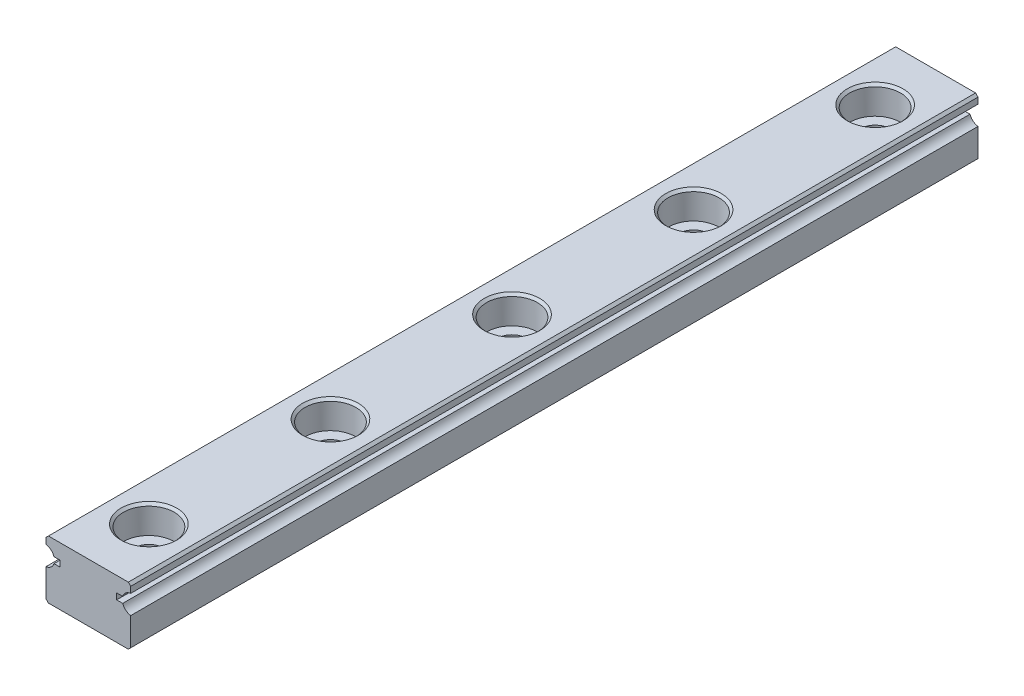
SolidWorks part; units mm, degrees
ref_plane "Спереди" through (0, 0, 0) normal (0, 0, 1) x (1, 0, 0)
ref_plane "Сверху" through (0, 0, 0) normal (0, 1, 0) x (1, 0, 0)
ref_plane "Справа" through (0, 0, 0) normal (1, 0, 0) x (0, 0, -1)
sketch "Sketch1" plane through (0, 0, 0) normal (0, 0, 1) x (1, 0, 0)
  line L0 (0, 0) -> (0, 4.3706) construction
  line L1 (-3.3, -2.4) -> (3.3, -2.4)
  line L2 (-3.5, -2.2) -> (-3.5, 0.1063)
  line L3 (-3.3, 2.4) -> (3.3, 2.4)
  line L4 (3.5, -2.2) -> (3.5, 0.1063)
  line L5 (-3.5, -2.4) -> (3.5, 2.4) construction
  line L6 (-3.5, 2.4) -> (3.5, -2.4) construction
  line L7 (-3.5, 1.6937) -> (-3.5, 2.2)
  line L8 (3.5, 1.6937) -> (3.5, 2.2)
  line L9 (-3.5, -2.2) -> (-3.3, -2.4)
  line L10 (3.3, -2.4) -> (3.5, -2.2)
  line L11 (3.3, 2.4) -> (3.5, 2.2)
  line L12 (-3.5, 2.2) -> (-3.3, 2.4)
  line L13 (2.8401, 0.65) -> (2.3401, 0.65)
  line L14 (-2.8401, 0.65) -> (-2.3401, 0.65)
  line L15 (2.3401, 0.65) -> (2.3401, 1.15)
  line L16 (-2.8401, 1.15) -> (-2.3401, 1.15)
  line L17 (-2.3401, 0.65) -> (-2.3401, 1.15)
  line L18 (2.8401, 1.15) -> (2.3401, 1.15)
  arc A0 (-3.5, 1.6937) -> (-2.8401, 1.15) centre (-3.6, 0.9) cw
  arc A1 (3.5, 1.6937) -> (2.8401, 1.15) centre (3.6, 0.9) ccw
  arc A2 (-2.8401, 0.65) -> (-3.5, 0.1063) centre (-3.6, 0.9) cw
  arc A3 (2.8401, 0.65) -> (3.5, 0.1063) centre (3.6, 0.9) ccw
  point P0 (0, 0)
  dimension "D4" = 0.8
  dimension "D5" = 0.1
  dimension "D1" = 7
  dimension "D2" = 4.8
  dimension "D3" = 1.5
  dimension "D6" = 0.5
  dimension "D7" = 0.5
extrude "Extrude1" add sketch "Sketch1" along normal blind 70
sketch "Sketch2" plane through (0, 2.4, 0) normal (0, 1, 0) x (1, 0, 0)
  line L0 (0, 0) -> (0, -5) construction
  circle A0 centre (0, -5) radius 1.2
  circle A1 centre (0, -5) radius 2.1
  dimension "D1" = 2.4
  dimension "D2" = 4.2
  dimension "D3" = 5
extrude "Extrude2" cut sketch "Sketch2" against normal up to next contours A0 region at (0, 2.4, 5)
extrude "Extrude4" cut sketch "Sketch" against normal blind 2.3
sketch "Sketch" plane through (0, 2.4, 0) normal (0, 1, 0) x (1, 0, 0) same geometry as "Sketch2"
chamfer "Chamfer1" distance 0.2 angle 45 2 edges at (0, -2.4, 6.2) (0, 2.4, 7.1)
pattern_linear "LPattern1" count 5 spacing 15 along (0, 0, 1) of "Extrude4", "Chamfer1", "Extrude2"
